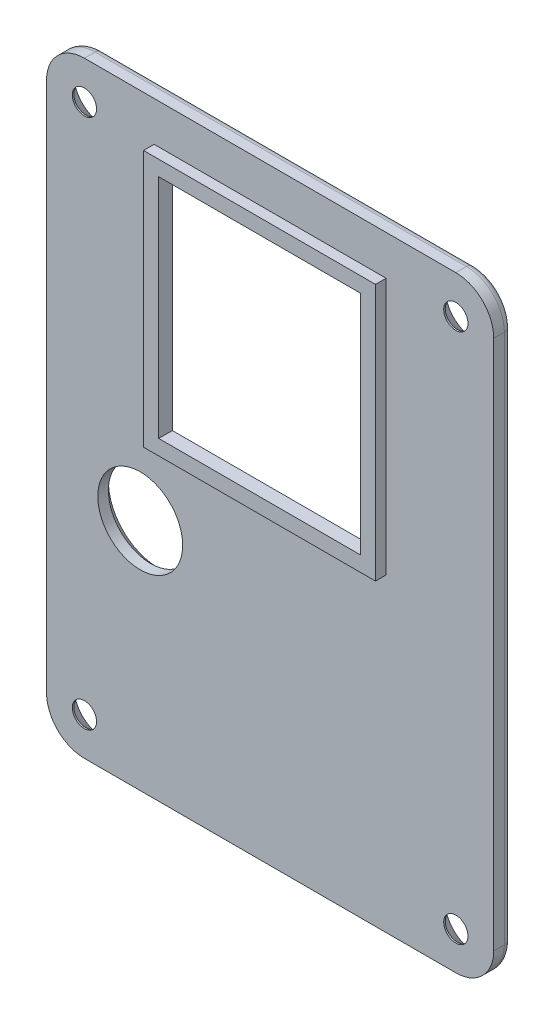
SolidWorks part; units mm, degrees
ref_plane "Спереди" through (0, 0, 0) normal (0, 0, 1) x (1, 0, 0)
ref_plane "Сверху" through (0, 0, 0) normal (0, 1, 0) x (1, 0, 0)
ref_plane "Справа" through (0, 0, 0) normal (1, 0, 0) x (0, 0, -1)
sketch "Эскиз1" plane through (0, 0, 0) normal (0, 0, 1) x (1, 0, 0)
  line L0 (29.5, 0) -> (29.5, -80) construction
  line L1 (0, 0) -> (59, 0)
  line L2 (0, 0) -> (0, -80)
  line L3 (0, -80) -> (59, -80)
  line L4 (59, 0) -> (59, -80)
  line L9 (29.5, -10) -> (29.5, -52.4) construction
  circle A1 centre (12.36, -49.17) radius 5.6
  dimension "D8" = 11.2
  dimension "D1" = 59
  dimension "D2" = 49.17
  dimension "D3" = 80
  dimension "D4" = 12.36
extrude "Бобышка-Вытянуть1" add sketch "Эскиз1" along normal blind 2.4
sketch "Эскиз4" plane through (0, 0, 2.4) normal (0, 0, 1) x (1, 0, 0)
  line L19 (0, 0) -> (59, 0)
  line L20 (0, 0) -> (0, -80)
  line L21 (0, -80) -> (59, -80)
  line L22 (59, 0) -> (59, -80)
  line L23 (5.1, -2) -> (53.9, -2)
  line L24 (2, -5.1) -> (2, -74.9)
  line L25 (5.1, -78) -> (53.9, -78)
  line L26 (57, -5.1) -> (57, -74.9)
  arc A0 (2, -74.9) -> (5.1, -78) centre (5.1, -74.9) ccw
  arc A1 (53.9, -78) -> (57, -74.9) centre (53.9, -74.9) ccw
  arc A2 (53.9, -2) -> (57, -5.1) centre (53.9, -5.1) cw
  arc A3 (5.1, -2) -> (2, -5.1) centre (5.1, -5.1) ccw
  dimension "D5" = 3.1
  dimension "D1" = 2
  dimension "D2" = 2
  dimension "D3" = 2
  dimension "D4" = 2
extrude "Бобышка-Вытянуть6" add sketch "Эскиз4" along normal blind 5.5
fillet "Скругление1" radius 5 1 edges at (0, 0, 3.95)
fillet "Скругление2" radius 5 3 edges at (0, -80, 3.95) (59, -80, 3.95) (59, 0, 3.95)
sketch "Эскиз14" plane through (0, 0, 2.4) normal (0, 0, 1) x (1, 0, 0)
  line L0 (0, -5) -> (0, -75) construction
  line L1 (59, -75) -> (59, -5) construction
  line L2 (5, -80) -> (54, -80) construction
  line L3 (5, -80) -> (54, -80) construction
  line L4 (54, 0) -> (5, 0) construction
  circle A0 centre (5, -5) radius 3
  circle A1 centre (5, -75) radius 3
  circle A2 centre (54, -75) radius 3
  circle A3 centre (54, -5) radius 3
  circle A4 centre (5, -5) radius 1.3
  circle A5 centre (54, -5) radius 1.3
  circle A6 centre (5, -75) radius 1.3
  circle A7 centre (54, -75) radius 1.3
  dimension "D1" = 5
  dimension "D2" = 5
  dimension "D3" = 5
  dimension "D4" = 5
  dimension "D5" = 5
  dimension "D6" = 5
  dimension "D7" = 5
  dimension "D8" = 5
  dimension "D9" = 2.6
  dimension "D10" = 6
  dimension "D11" = 2.6
extrude "Бобышка-Вытянуть7" add sketch "Эскиз14" along normal blind 6.5
sketch "Эскиз15" plane through (0, 0, 7.9) normal (0, 0, 1) x (1, 0, 0)
  line L0 (5, -80) -> (54, -80) construction
  line L5 (5, 0) -> (54, 0)
  line L6 (0, -5) -> (0, -75)
  line L7 (5, -80) -> (54, -80)
  line L8 (59, -5) -> (59, -75)
  line L9 (59, -75) -> (59, -5) construction
  line L10 (5, -1) -> (54, -1)
  line L11 (1, -5) -> (1, -75)
  line L12 (5, -79) -> (54, -79)
  line L13 (58, -5) -> (58, -75)
  arc A0 (0, -75) -> (5, -80) centre (5, -75) ccw
  arc A1 (54, -80) -> (59, -75) centre (54, -75) ccw
  arc A2 (54, 0) -> (59, -5) centre (54, -5) cw
  arc A3 (5, 0) -> (0, -5) centre (5, -5) ccw
  arc A4 (5, -1) -> (1, -5) centre (5, -5) ccw
  arc A5 (54, -1) -> (58, -5) centre (54, -5) cw
  arc A6 (54, -79) -> (58, -75) centre (54, -75) ccw
  arc A7 (1, -75) -> (5, -79) centre (5, -75) ccw
  point P23 (0, 0)
  dimension "D5" = 5
  dimension "D6" = 4
  dimension "D1" = 1
  dimension "D2" = 1
  dimension "D3" = 1
  dimension "D4" = 1
extrude "Бобышка-Вытянуть10" add sketch "Эскиз15" along normal blind 1 separate body
fillet "Скругление3" radius 1 8 edges at (57.5355, -1.4645, 0) (59, -40, 0) (57.5355, -78.5355, 0) (29.5, -80, 0) (1.4645, -78.5355, 0) (0, -40, 0) (1.4645, -1.4645, 0) (29.5, 0, 0)
sketch "Эскиз20" plane through (59, 0, 0) normal (1, 0, 0) x (0, 0, -1)
  line L0 (-8.9, -75) -> (-8.9, -5) construction
  line L1 (-8.9, -11.15) -> (-5.2, -11.15)
  line L2 (-8.9, -11.15) -> (-8.9, -19.25)
  line L3 (-8.9, -19.25) -> (-5.2, -19.25)
  line L4 (-4.2, -12.15) -> (-4.2, -18.25)
  line L5 (-7.9, 0) -> (-1, 0) construction
  arc A0 (-5.2, -19.25) -> (-4.2, -18.25) centre (-5.2, -18.25) ccw
  arc A1 (-5.2, -11.15) -> (-4.2, -12.15) centre (-5.2, -12.15) cw
  point P10 (-4.2, -19.25)
  point P13 (-4.2, -11.15)
  dimension "D4" = 1
  dimension "D1" = 8.1
  dimension "D2" = 4.7
  dimension "D3" = 11.15
extrude "Вырез-Вытянуть1" cut sketch "Эскиз20" against normal blind 10
sketch "Эскиз23" plane through (0, 0, 0) normal (0, 0, -1) x (-1, 0, 0)
  line L1 (-16.2, -7.241) -> (-42.8, -7.241)
  line L2 (-16.2, -7.241) -> (-16.2, -37.141)
  line L3 (-16.2, -37.141) -> (-42.8, -37.141)
  line L4 (-42.8, -7.241) -> (-42.8, -37.141)
  dimension "D1" = 29.9
  dimension "D2" = 26.6
extrude "Вырез-Вытянуть4" cut sketch "Эскиз23" against normal blind 52
ref_axis "Ось1" through (29.5, -1, 0) along (0, -1, 0)
sketch "Эскиз24" plane through (0, 0, 2.4) normal (0, 0, 1) x (1, 0, 0)
  line L0 (42.8, -7.241) -> (16.2, -7.241)
  line L1 (42.8, -7.241) -> (42.8, -2.241)
  line L2 (16.2, -7.241) -> (16.2, -2.241)
  line L3 (42.8, -2.241) -> (16.2, -2.241)
  dimension "D1" = 5
extrude "Бобышка-Вытянуть11" add sketch "Эскиз24" along normal blind 0.2
sketch "Эскиз25" plane through (0, 0, 2.4) normal (0, 0, 1) x (1, 0, 0)
  line L0 (16.2, -37.141) -> (42.8, -37.141)
  line L1 (16.2, -37.141) -> (16.2, -42.141)
  line L2 (42.8, -37.141) -> (42.8, -42.141)
  line L3 (16.2, -42.141) -> (42.8, -42.141)
  line L4 (16.2, -37.141) -> (42.8, -37.141) construction
  dimension "D1" = 5
extrude "Бобышка-Вытянуть12" add sketch "Эскиз25" along normal blind 0.2 contours L3 L2 L0 L1
sketch "Эскиз26" plane through (0, 0, 2.4) normal (0, 0, 1) x (1, 0, 0)
  circle A0 centre (46.9, -5.7) radius 1.3
  circle A1 centre (54, -5) radius 1.3 construction
  arc A3 (53.9504, -2.0004) -> (56.9996, -5.0496) centre (54, -5) ccw construction
  circle A4 centre (54, -5) radius 1.3 construction
  circle A5 centre (46.9, -5.7) radius 3.1474
  dimension "D1" = 2.6
  dimension "D3" = 0.7
  dimension "D4" = 7.1
  dimension "D2" = 3
extrude "Бобышка-Вытянуть13" add sketch "Эскиз26" along normal blind 6.5
sketch "Эскиз27" plane through (0, 0, 7.9) normal (0, 0, 1) x (1, 0, 0)
  line L12 (58, -75) -> (58, -19.25)
  line L13 (58, -19.25) -> (57, -19.25)
  line L14 (57, -19.25) -> (57, -74.9)
  line L15 (53.9, -78) -> (5.1, -78)
  line L16 (2, -74.9) -> (2, -5.1)
  line L17 (5.1, -2) -> (53.9, -2)
  line L18 (57, -5.1) -> (57, -11.15)
  line L19 (57, -11.15) -> (58, -11.15)
  line L20 (58, -11.15) -> (58, -5)
  line L21 (54, -1) -> (5, -1)
  line L22 (1, -5) -> (1, -75)
  line L23 (5, -79) -> (54, -79)
  line L24 (58, -75) -> (58, -19.25)
  line L25 (58, -19.25) -> (57, -19.25)
  line L26 (57, -19.25) -> (57, -74.9)
  line L27 (53.9, -78) -> (5.1, -78)
  line L28 (2, -74.9) -> (2, -5.1)
  line L29 (5.1, -2) -> (53.9, -2)
  line L30 (57, -5.1) -> (57, -11.15)
  line L31 (57, -11.15) -> (58, -11.15)
  line L32 (58, -11.15) -> (58, -5)
  line L33 (54, -1) -> (5, -1)
  line L34 (1, -5) -> (1, -75)
  line L35 (5, -79) -> (54, -79)
  arc A16 (54, -79) -> (58, -75) centre (54, -75) ccw
  arc A17 (56.9996, -74.9504) -> (57, -74.9) centre (53.9, -74.9) ccw
  arc A18 (53.9504, -77.9996) -> (56.9996, -74.9504) centre (54, -75) ccw
  arc A19 (53.9, -78) -> (53.9504, -77.9996) centre (53.9, -74.9) ccw
  arc A20 (5.0496, -77.9996) -> (5.1, -78) centre (5.1, -74.9) ccw
  arc A21 (2.0004, -74.9504) -> (5.0496, -77.9996) centre (5, -75) ccw
  arc A22 (2, -74.9) -> (2.0004, -74.9504) centre (5.1, -74.9) ccw
  arc A23 (2.0004, -5.0496) -> (2, -5.1) centre (5.1, -5.1) ccw
  arc A24 (5.0496, -2.0004) -> (2.0004, -5.0496) centre (5, -5) ccw
  arc A25 (5.1, -2) -> (5.0496, -2.0004) centre (5.1, -5.1) ccw
  arc A26 (53.9504, -2.0004) -> (53.9, -2) centre (53.9, -5.1) ccw
  arc A27 (56.9996, -5.0496) -> (53.9504, -2.0004) centre (54, -5) ccw
  arc A28 (57, -5.1) -> (56.9996, -5.0496) centre (53.9, -5.1) ccw
  arc A29 (58, -5) -> (54, -1) centre (54, -5) ccw
  arc A30 (5, -1) -> (1, -5) centre (5, -5) ccw
  arc A31 (1, -75) -> (5, -79) centre (5, -75) ccw
  arc A32 (54, -79) -> (58, -75) centre (54, -75) ccw
  arc A33 (56.9996, -74.9504) -> (57, -74.9) centre (53.9, -74.9) ccw
  arc A34 (53.9504, -77.9996) -> (56.9996, -74.9504) centre (54, -75) ccw
  arc A35 (53.9, -78) -> (53.9504, -77.9996) centre (53.9, -74.9) ccw
  arc A36 (5.0496, -77.9996) -> (5.1, -78) centre (5.1, -74.9) ccw
  arc A37 (2.0004, -74.9504) -> (5.0496, -77.9996) centre (5, -75) ccw
  arc A38 (2, -74.9) -> (2.0004, -74.9504) centre (5.1, -74.9) ccw
  arc A39 (2.0004, -5.0496) -> (2, -5.1) centre (5.1, -5.1) ccw
  arc A40 (5.0496, -2.0004) -> (2.0004, -5.0496) centre (5, -5) ccw
  arc A41 (5.1, -2) -> (5.0496, -2.0004) centre (5.1, -5.1) ccw
  arc A42 (53.9504, -2.0004) -> (53.9, -2) centre (53.9, -5.1) ccw
  arc A43 (56.9996, -5.0496) -> (53.9504, -2.0004) centre (54, -5) ccw
  arc A44 (57, -5.1) -> (56.9996, -5.0496) centre (53.9, -5.1) ccw
  arc A45 (58, -5) -> (54, -1) centre (54, -5) ccw
  arc A46 (5, -1) -> (1, -5) centre (5, -5) ccw
  arc A47 (1, -75) -> (5, -79) centre (5, -75) ccw
  dimension "D1" = 0
extrude "Вырез-Вытянуть5" cut sketch "Эскиз27" against normal blind 0.6
sketch "Эскиз28" plane through (0, 0, 2.4) normal (0, 0, 1) x (1, 0, 0)
  line L0 (5, -2) -> (8, -2)
  line L1 (53.9, -2) -> (5.1, -2) construction
  line L2 (8, -2) -> (8, -5)
  line L4 (5, -8) -> (2, -8)
  line L5 (2, -5.1) -> (2, -74.9) construction
  line L6 (2, -8) -> (2, -5.1)
  line L7 (2, -5.1) -> (2.0017, -5.1017)
  line L8 (51, -5) -> (51, -2)
  line L9 (57, -74.9) -> (57, -5.1) construction
  line L10 (57, -8) -> (54, -8)
  line L12 (57, -5) -> (57, -8)
  line L13 (5.1, -2) -> (53.9, -2) construction
  line L14 (51, -2) -> (54, -2)
  line L16 (43.7526, -5.7) -> (43.7526, -2)
  line L17 (43.7526, -2) -> (50.0474, -2)
  line L18 (50.0474, -2) -> (50.0474, -5.7)
  circle A0 centre (5, -5) radius 3 construction
  arc A1 (2.0004, -5.0496) -> (5.0496, -2.0004) centre (5, -5) ccw construction
  arc A2 (53.9504, -2.0004) -> (56.9996, -5.0496) centre (54, -5) ccw construction
  arc A3 (56.9996, -5.0496) -> (53.9504, -2.0004) centre (54, -5) ccw construction
  circle A4 centre (54, -5) radius 3 construction
  circle A5 centre (46.9, -5.7) radius 3.1474 construction
  circle A6 centre (46.9, -5.7) radius 3.1474 construction
  arc A12 (2.0017, -5.1017) -> (5, -8) centre (5, -5) ccw
  arc A13 (8, -5) -> (5, -2) centre (5, -5) ccw
  arc A14 (50.0474, -5.7) -> (43.7526, -5.7) centre (46.9, -5.7) ccw
  arc A15 (54, -2) -> (51, -5) centre (54, -5) ccw
  arc A16 (54, -8) -> (57, -5) centre (54, -5) ccw
chamfer "Фаска1" distance 2 angle 45 4 edges at (42.8, -22.191, 0) (29.5, -7.241, 0) (16.2, -22.191, 0) (29.5, -37.141, 0)
chamfer "Фаска2" distance 1 angle 45 1 edges at (17.96, -49.17, 0)
sketch "Эскиз30" plane through (0, 0, 2.4) normal (0, 0, 1) x (1, 0, 0)
  line L0 (54, -72) -> (57, -72)
  line L1 (57, -74.9) -> (57, -5.1) construction
  line L2 (57, -72) -> (57, -75)
  line L3 (54, -72) -> (51, -72)
  line L4 (51, -72) -> (51, -75)
  line L5 (51, -75) -> (51, -78)
  line L6 (5.1, -78) -> (53.9, -78) construction
  line L7 (51, -78) -> (54, -78)
  line L8 (8, -75) -> (8, -72)
  line L9 (8, -72) -> (5, -72)
  line L10 (5, -72) -> (2, -72)
  line L11 (2, -74.9) -> (2, -5.1) construction
  line L12 (2, -72) -> (2.0004, -74.9504)
  line L13 (8, -75) -> (8, -78)
  line L14 (8, -78) -> (5.0496, -77.9996)
  arc A0 (57, -75) -> (54, -78) centre (54, -75) ccw
  arc A1 (5.0496, -77.9996) -> (2.0004, -74.9504) centre (5, -75) ccw construction
  circle A2 centre (5, -75) radius 3 construction
  arc A3 (5.0496, -77.9996) -> (2.0004, -74.9504) centre (5, -75) ccw
  arc M12 (2.0004, -74.9504) -> (5.0496, -77.9996) centre (5, -75) cw
  line M14 (5.1, -78) -> (53.9, -78)
  arc M15 (53.9, -78) -> (53.9504, -77.9996) centre (53.9, -74.9) ccw
  arc M16 (53.9504, -77.9996) -> (56.9996, -74.9504) centre (54, -75) cw
  arc M17 (56.9996, -74.9504) -> (57, -74.9) centre (53.9, -74.9) ccw
  line M18 (57, -74.9) -> (57, -5.1)
extrude "Бобышка-Вытянуть16" add sketch "Эскиз30" along normal up to surface (6.5 mm away) separate body contours L14 L13 M12 | L8 L9 M12 | L10 L12 M12 | L0 M16 M17 M18 | L3 L4 M16 | L5 M16 M14 M15 region at (51.6701, -72.6701, 2.4) region at (56.3299, -72.6701, 2.4) region at (2.6703, -72.6697, 2.4) region at (7.3299, -72.6701, 2.4) region at (7.3303, -77.3297, 2.4) region at (51.6701, -77.3299, 2.4) up to face at (57, -75, 8.9)
sketch "Эскиз31" plane through (0, 0, 2.4) normal (0, 0, 1) x (1, 0, 0)
  line L0 (5, -2) -> (8, -2)
  line L1 (8, -2) -> (8, -5)
  line L2 (8, -5) -> (5, -2)
  line L3 (5, -8) -> (2, -8)
  line L4 (2, -8) -> (2, -5.1)
  line L5 (2, -5.1) -> (5, -8)
  line L6 (50.0474, -5.7) -> (50.0474, -2)
  line L7 (50.0474, -2) -> (43.7526, -2)
  line L8 (43.7526, -2) -> (43.7539, -5.7904)
  line L9 (43.7539, -5.7904) -> (46.9, -2.5526)
  line L10 (46.9, -2.5526) -> (50.0474, -5.7)
  line L11 (57, -5) -> (54, -8)
  line L12 (54, -8) -> (57, -8)
  line L13 (57, -8) -> (57, -5)
  line L14 (54, -2) -> (51, -2)
  line L15 (51, -2) -> (51, -5)
  line L16 (51, -5) -> (54, -2)
  circle A0 centre (46.9, -5.7) radius 3.1474 construction
  arc A1 (50.0474, -5.7) -> (43.7526, -5.7) centre (46.9, -5.7) ccw construction
extrude "Бобышка-Вытянуть17" add sketch "Эскиз31" along normal up to surface (6.5 mm away) up to face at (50.0474, -5.7, 8.9)
sketch "Эскиз32" plane through (0, 0, 2.4) normal (0, 0, 1) x (1, 0, 0)
  line L0 (-1.9989, -9.1808) -> (60.3488, -9.1808)
  line L1 (60.3488, -9.1808) -> (59.1078, -83.5252)
  line L2 (59.1078, -83.5252) -> (-8.3232, -82.3995)
  line L3 (-8.3232, -82.3995) -> (-1.9989, -9.1808)
sketch "Эскиз34" plane through (0, 0, 8.9) normal (0, 0, 1) x (1, 0, 0)
  circle A0 centre (5, -75) radius 1.3
  circle A1 centre (54, -75) radius 1.3
  circle A2 centre (54, -5) radius 1.3
  circle A3 centre (5, -5) radius 1.3
extrude "Вырез-Вытянуть7" cut sketch "Эскиз34" against normal blind 10
sketch "Эскиз33" plane through (0, 0, 2.4) normal (0, 0, 1) x (1, 0, 0)
  line L1 (-4.6528, 3.8656) -> (66.1187, 3.8656)
  line L2 (-4.6528, 3.8656) -> (-4.6528, -86.8355)
  line L3 (-4.6528, -86.8355) -> (66.1187, -86.8355)
  line L4 (66.1187, 3.8656) -> (66.1187, -86.8355)
extrude "Вырез-Вытянуть6" cut sketch "Эскиз33" along normal blind 10 contours L2 L3 L4 L1
chamfer "Фаска3" distance 2.5 angle 45 4 edges at (6.3, -5, 0) (6.3, -75, 0) (55.3, -75, 0) (55.3, -5, 0)
sketch "Эскиз35" plane through (0, 0, 2.4) normal (0, 0, 1) x (1, 0, 0)
  line L1 (14.2, -5.241) -> (44.8, -5.241)
  line L2 (14.2, -5.241) -> (14.2, -39.141)
  line L3 (14.2, -39.141) -> (44.8, -39.141)
  line L4 (44.8, -5.241) -> (44.8, -39.141)
  line L5 (16.2, -7.241) -> (42.8, -7.241)
  line L6 (16.2, -7.241) -> (16.2, -37.141)
  line L7 (16.2, -37.141) -> (42.8, -37.141)
  line L8 (42.8, -7.241) -> (42.8, -37.141)
  dimension "D1" = 2
  dimension "D2" = 2
  dimension "D3" = 2
  dimension "D4" = 2
extrude "Бобышка-Вытянуть18" add sketch "Эскиз35" along normal blind 1.4
sketch "Эскиз36" plane through (0, 0, 2.4) normal (0, 0, 1) x (1, 0, 0)
  line L0 (24.2851, -42.7807) -> (47.3615, -41.8551)
  line L1 (47.3615, -41.8551) -> (49.7061, -12.6704)
  line L2 (49.7061, -12.6704) -> (55.3827, -14.1512)
  line L3 (55.3827, -14.1512) -> (53.2848, -67.4612)
  line L4 (53.2848, -67.4612) -> (46.7445, -76.3462)
  line L5 (46.7445, -76.3462) -> (12.5002, -75.7292)
  line L6 (12.5002, -75.7292) -> (4.6024, -64.3144)
  line L7 (4.6024, -64.3144) -> (12.5002, -57.2188)
  line L8 (12.5002, -57.2188) -> (19.5958, -58.4528)
  line L9 (19.5958, -58.4528) -> (24.2851, -42.7807)
  line L10 (11.7979, -30.8861) -> (10.2409, -9.1808)
  line L11 (-1.9989, -9.1808) -> (60.3488, -9.1808) construction
  line L12 (10.2409, -9.1808) -> (2.6288, -9.7268)
  line L13 (2.6288, -9.7268) -> (2.0333, -42.7807)
  line L14 (2.0333, -42.7807) -> (10.1555, -37.7828)
  line L15 (10.1555, -37.7828) -> (11.7979, -30.8861)
  point P17 (11.7979, -31.236)
sketch "Эскиз38" plane through (0, 0, 0) normal (0, 0, -1) x (-1, 0, 0)
  line L0 (-64.7613, -13.9044) -> (-41.6232, -11.8066)
  line L1 (-41.6232, -11.8066) -> (-41.6232, 7.1358)
  line L2 (-41.6232, 7.1358) -> (13.1059, 1.089)
  line L3 (13.1059, 1.089) -> (10.8847, -89.6737)
  line L4 (10.8847, -89.6737) -> (-75.559, -88.4397)
  line L5 (-75.559, -88.4397) -> (-64.7613, -13.9044)
sketch "Эскиз37" plane through (0, 0, 2.4) normal (0, 0, 1) x (1, 0, 0)
  circle A0 centre (5, -5) radius 1.6
  circle A1 centre (54, -5) radius 1.6
  circle A2 centre (54, -75) radius 1.6
  circle A3 centre (5, -75) radius 1.6
  dimension "D1" = 3.2
extrude "Вырез-Вытянуть11" cut sketch "Эскиз37" against normal blind 11.4
